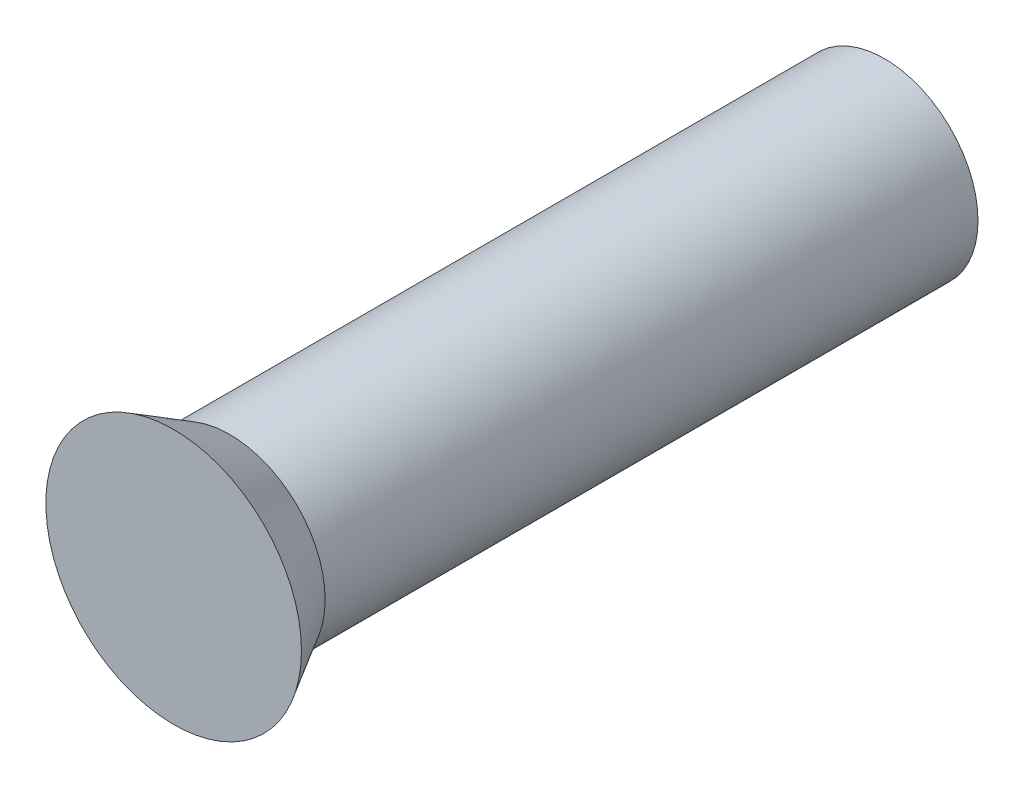
SolidWorks part; units mm, degrees
ref_plane "Front Plane" through (0, 0, 0) normal (0, 0, 1) x (1, 0, 0)
ref_plane "Top Plane" through (0, 0, 0) normal (0, 1, 0) x (1, 0, 0)
ref_plane "Right Plane" through (0, 0, 0) normal (1, 0, 0) x (0, 0, -1)
sketch "Sketch1" plane through (0, 0, 0) normal (0, 0, 1) x (1, 0, 0)
  circle A0 centre (0, 0) radius 0.5
  dimension "D1" = 1
extrude "Boss-Extrude1" add sketch "Sketch1" along normal blind 3.5
sketch "Sketch2" plane through (0, 0, 3.5) normal (0, 0, 1) x (1, 0, 0)
  circle A0 centre (0, 0) radius 0.75
  dimension "D1" = 1.5
extrude "Boss-Extrude2" add sketch "Sketch2" along normal blind 0.3
chamfer "Chamfer1" distance 0.24 angle 60 1 edges at (0.75, 0, 3.5) first distance on face at (0.5, 0, 3.5)
